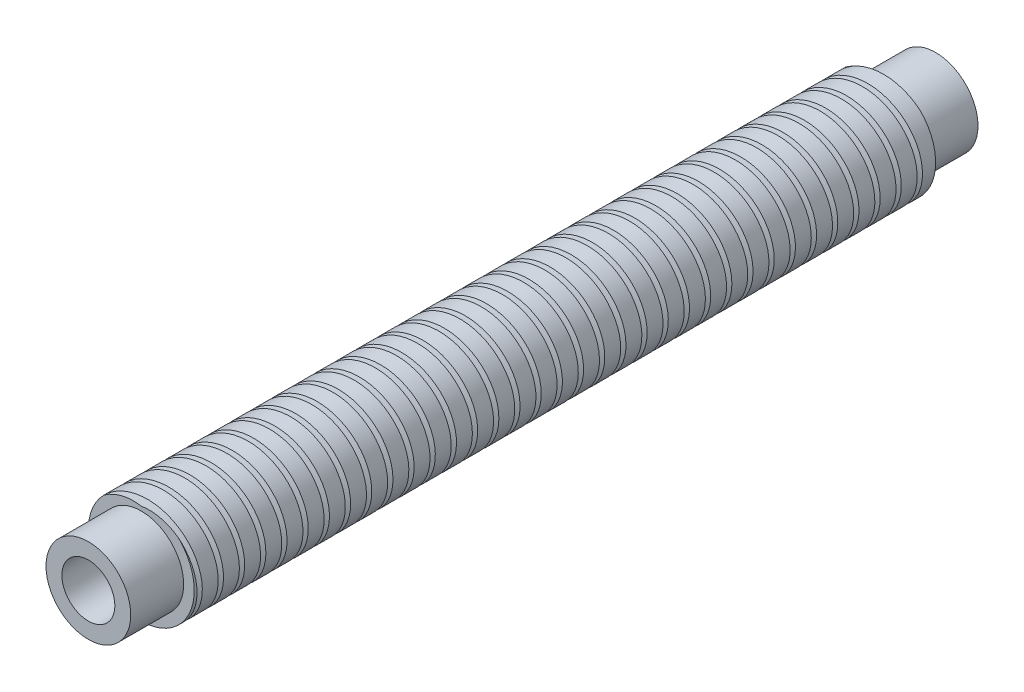
SolidWorks part; units mm, degrees
material "1060-H12 Rod (SS)"
ref_plane "Front Plane" through (0, 0, 0) normal (0, 0, 1) x (1, 0, 0)
ref_plane "Top Plane" through (0, 0, 0) normal (0, 1, 0) x (1, 0, 0)
ref_plane "Right Plane" through (0, 0, 0) normal (1, 0, 0) x (0, 0, -1)
sketch "Sketch1" plane through (0, 0, 0) normal (0, 0, 1) x (1, 0, 0)
  circle A0 centre (0, 0) radius 4
  dimension "D1" = 8
extrude "Boss-Extrude1" add sketch "Sketch1" along normal blind 5
sketch "Sketch2" plane through (0, 0, 5) normal (0, 0, 1) x (1, 0, 0)
  circle A0 centre (0, 0) radius 5
  dimension "D1" = 10
extrude "Boss-Extrude2" add sketch "Sketch2" along normal blind 35
ref_plane "Plane1" through (0, 0, 40) normal (0, 0, 1) x (1, 0, 0)
mirror "Mirror1" about plane through (0, 0, 40) normal (0, 0, 1) of "Boss-Extrude2", "Boss-Extrude1"
sketch "Sketch3" plane through (0, 0, 75) normal (0, 0, 1) x (1, 0, 0)
  circle A0 centre (0, 0) radius 4
  dimension "D1" = 8
extrude "Boss-Extrude3" add sketch "Sketch3" along normal blind 5
sketch "Sketch4" plane through (0, 0, 0) normal (1, 0, 0) x (0, 0, -1)
  line L0 (-5, 5) -> (-4.75, 5)
  line L1 (-4.75, 5) -> (-5, 4.3964)
  line L2 (-5, -5) -> (-5, 5) construction
  line L3 (-5, 4.3964) -> (-5.25, 5)
  line L4 (-5, 5) -> (-75, 5) construction
  line L5 (-5.25, 5) -> (-5, 5)
  dimension "D1" = 45
  dimension "D2" = 0.25
sketch "Sketch5" plane through (0, 0, 5) normal (0, 0, -1) x (-1, 0, 0)
  circle A0 centre (0, 0) radius 5 construction
  circle A1 centre (0, 0) radius 5
curve "Helix/Spiral1" pitch 2 height 72 turns 36
sketch "Sketch6" plane through (0, 0, 80) normal (0, 0, 1) x (1, 0, 0)
  circle A0 centre (0, 0) radius 2.5
  dimension "D1" = 5
extrude "Cut-Extrude1" cut sketch "Sketch6" against normal blind 10
sweep "Cut-Sweep3" cut profiles "Sketch4" path "Helix/Spiral1"
